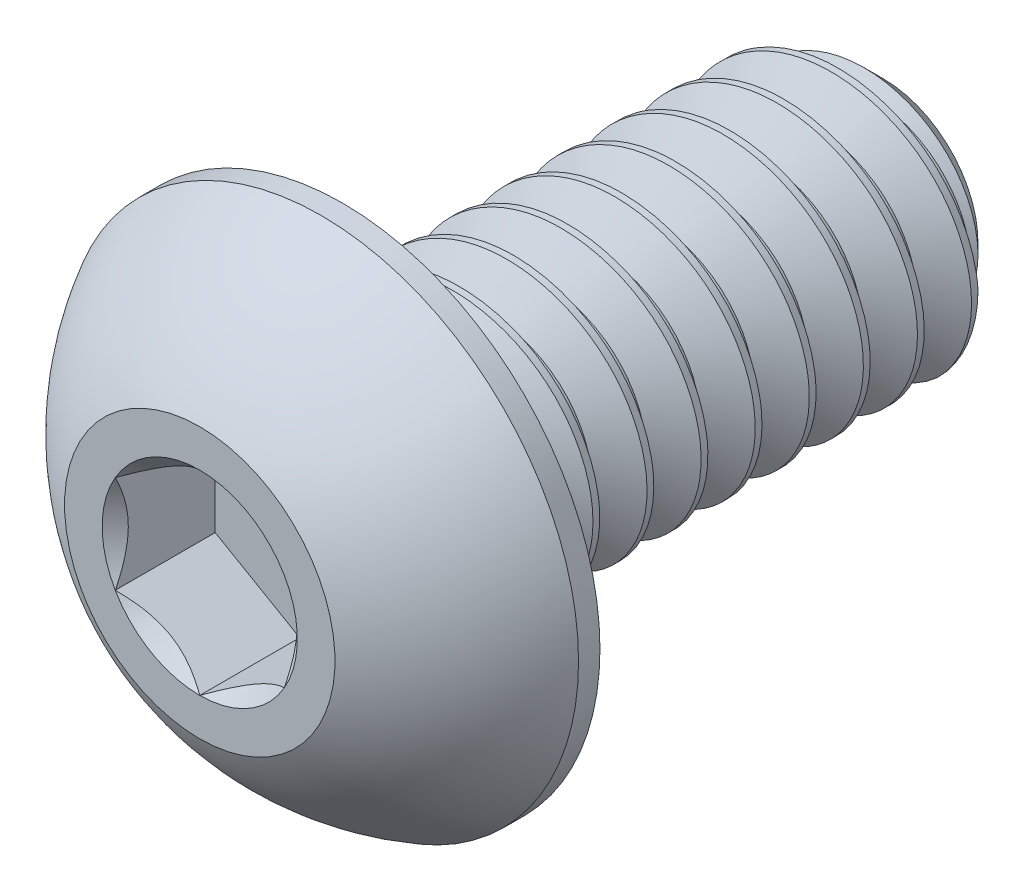
SolidWorks part; units mm, degrees
ref_plane "Front" through (0, 0, 0) normal (0, 0, 1) x (1, 0, 0)
ref_plane "Top" through (0, 0, 0) normal (0, 1, 0) x (1, 0, 0)
ref_plane "Right" through (0, 0, 0) normal (1, 0, 0) x (0, 0, -1)
sketch "Sketch1" plane through (0, 0, 0) normal (1, 0, 0) x (0, 0, -1)
  line L2 (1.6764, 1.5875) -> (8.0264, 1.5875)
  line L3 (8.0264, 1.5875) -> (8.0264, 0)
  line L4 (8.0264, 0) -> (1.6764, 0)
  line L6 (1.4249, 3.0226) -> (1.6764, 3.0226) construction
  line L7 (8.0264, 1.5875) -> (8.0264, -1.5875) construction
  line L8 (0, 0) -> (1.6764, 0) construction
  line L9 (1.6764, 3.0226) -> (1.6764, -3.0226) construction
  line L11 (1.6764, 1.5875) -> (1.6764, 0)
  line L13 (0, 0.9922) -> (0, -0.9922) construction
  line L14 (0, 0.9922) -> (0, 1.5875) construction
  arc A3 (0, 1.5875) -> (1.4249, 3.0226) centre (3.034, 0) cw construction
  dimension "D1" = 0.2515
  dimension "Head Ht" = 1.6764
  dimension "Head Dia" = 6.0452
  dimension "Dia" = 3.175
  dimension "Lg" = 6.35
  dimension "Hex" = 1.9844
revolve "Revolve1" add sketch "Sketch1" angle 360 mid plane about L4
sketch "Sketch3" plane through (0, 0, -8.0264) normal (0, 0, -1) x (-1, 0, 0)
  circle A0 centre (0, 0) radius 1.5875
curve "Helix/Spiral1" pitch 0.635 height 6.985 radius 1.5875 centre (0, 0, -8.0264) axis (0, 0, 1) start towards (0, 1, 0)
sketch "Sketch2" plane through (0, 0, 0) normal (1, 0, 0) x (0, 0, -1)
  line L0 (8.0264, 1.5875) -> (8.582, 1.5875)
  line L1 (8.582, 1.5875) -> (8.3439, 1.1751)
  line L2 (8.3439, 1.1751) -> (8.2645, 1.1751)
  line L3 (8.2645, 1.1751) -> (8.0264, 1.5875)
  line L4 (8.1455, 1.3813) -> (8.463, 1.3813) construction
  dimension "D1" = 60
  dimension "D2" = 0.0794
  dimension "D3" = 0.3175
chamfer "Chamfer1" distance 0.4763 angle 45 1 edges at (0, 1.5875, -8.0264)
sweep "Cut-Sweep1" cut profiles "Sketch2" path "Helix/Spiral1"
sketch "Sketch7" plane through (0, 0, 0) normal (1, 0, 0) x (0, 0, -1)
  line L6 (1.4249, 3.0226) -> (1.6764, 3.0226) construction
  line L8 (0, 0) -> (1.6764, 0) construction
  line L11 (1.6764, 3.0226) -> (1.6764, -3.0226) construction
  line L12 (1.4249, 3.0226) -> (1.6764, 3.0226)
  line L13 (0, 0) -> (1.6764, 0)
  line L14 (0, 0.9922) -> (0, -0.9922) construction
  line L15 (1.6764, 3.0226) -> (1.6764, 0)
  line L16 (0, 1.5875) -> (0, 0)
  arc A2 (1.4249, 3.0226) -> (0, 1.5875) centre (3.034, 0) ccw construction
  arc A3 (1.4249, 3.0226) -> (0, 1.5875) centre (3.034, 0) ccw
revolve "Revolve2" add sketch "Sketch7" angle 360 mid plane about L13
sketch "Sketch5" plane through (0, 0, 0) normal (0, 0, 1) x (1, 0, 0)
  line L1 (0.9922, -0.5728) -> (0.9922, 0.5728)
  line L2 (0.9922, 0.5728) -> (0, 1.1457)
  line L3 (0, 1.1457) -> (-0.9922, 0.5728)
  line L4 (-0.9922, 0.5728) -> (-0.9922, -0.5728)
  line L5 (-0.9922, -0.5728) -> (0, -1.1457)
  line L6 (0, -1.1457) -> (0.9922, -0.5728)
  circle A0 centre (0, 0) radius 0.9922 construction
extrude "Cut-Extrude2" cut sketch "Sketch5" against normal blind 1.1735
sketch "Sketch6" plane through (0, 0, 0) normal (0, 0, 1) x (1, 0, 0)
  circle A0 centre (0, 0) radius 1.1457
extrude "Cut-Extrude3" cut sketch "Sketch6" against normal blind 1.1735 draft 45
sketch "Sketch9" [suppressed] plane through (0, 0, -5.0546) normal (0, 0, 1) x (1, 0, 0)
  circle A2 centre (0, 0) radius 4.7625
extrude "Boss-Extrude2" [suppressed] add sketch "Sketch9" against normal offset from surface (12.7 mm away) 31.75 up to face at (0, 1.1113, -8.0264)
sketch "Sketch10" plane through (0, 0, 0) normal (1, 0, 0) x (0, 0, -1)
  line L0 (8.0264, 1.5875) -> (8.0264, -1.5875) construction
  point P0 (7.0739, -1.5875)
  dimension "D1" = 0.9525
equation "\"D3@Helix/Spiral1\" = \"Lg@Sketch1\" + \"D4@Helix/Spiral1\""
equation "\"D2@Sketch2\" = \"D4@Helix/Spiral1\" * .125"
equation "\"D3@Sketch2\" = \"D4@Helix/Spiral1\" * .5"
equation "\"D1@Chamfer1\" = \"D4@Helix/Spiral1\" * .75"
equation "\"D1@Cut-Extrude2\" = \"Head Ht@Sketch1\" * .7"
equation "\"D1@Sketch1\" = \"Head Ht@Sketch1\" * .15"
equation "\"D1@Sketch10\" = \"D4@Helix/Spiral1\" * 1.5"
equation "\"D1@Cut-Extrude3\" = \"D1@Cut-Extrude2\""
